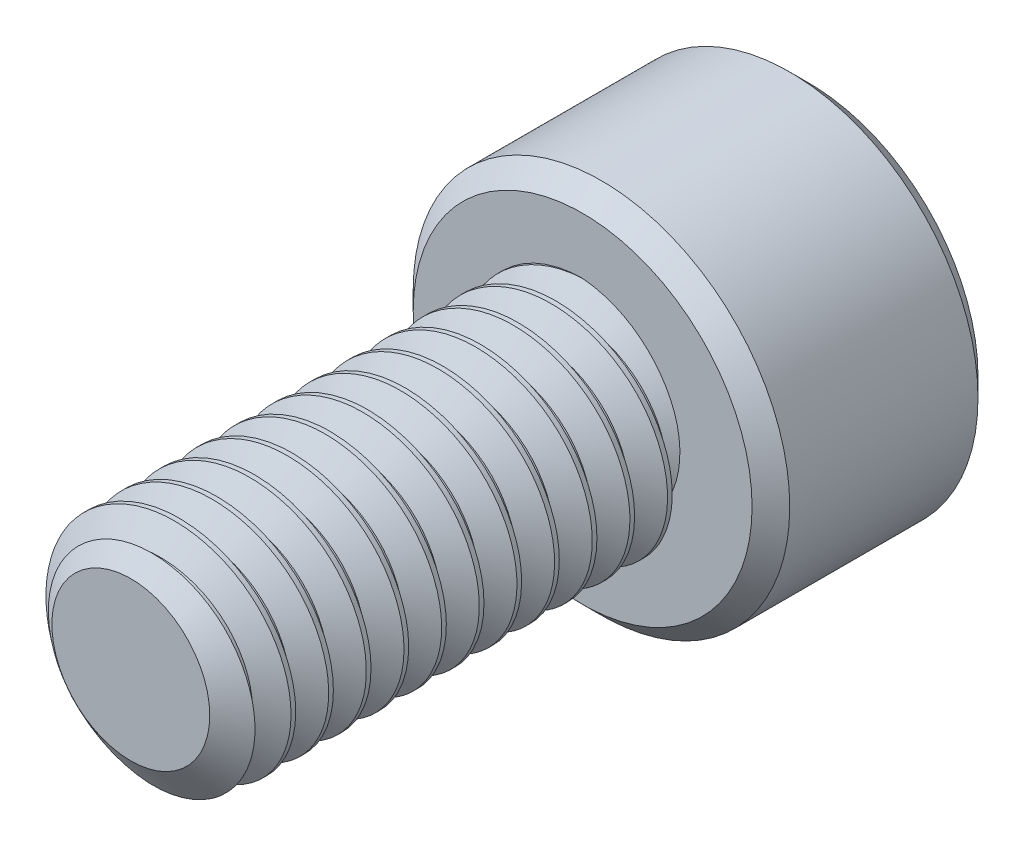
SolidWorks part; units mm, degrees
other "DetailItem1"
material "AISI Type 316L stainless steel"
ref_plane "Front Plane" through (0, 0, 0) normal (0, 0, 1) x (1, 0, 0)
ref_plane "Top Plane" through (0, 0, 0) normal (0, 1, 0) x (1, 0, 0)
ref_plane "Right Plane" through (0, 0, 0) normal (1, 0, 0) x (0, 0, -1)
sketch "Sketch1" plane through (0, 0, 0) normal (0, 0, 1) x (1, 0, 0)
  circle A0 centre (0, 0) radius 3
  dimension "OD" = 6
extrude "Extrude1" add sketch "Sketch1" against normal blind 12
sketch "Sketch2" plane through (0, 0, 0) normal (0, 0, 1) x (1, 0, 0)
  circle A0 centre (0, 0) radius 3 construction
  circle A1 centre (0, 0) radius 3
curve "Helix/Spiral1" pitch 1 height 13 turns 13 parameters "pitch"=1
sketch "Sketch3" plane through (0, 0, 0) normal (1, 0, 0) x (0, 0, -1)
  line L0 (-0.875, 3) -> (-0.5, 2.3505)
  line L1 (-0.5, 2.3505) -> (-0.375, 2.3505)
  line L2 (-0.375, 2.3505) -> (0, 3)
  line L3 (-0.875, 3) -> (0, 3)
  line L4 (-0.4375, 3) -> (-0.4375, 2.3505) construction
  line L5 (-0.6875, 2.6752) -> (-0.1875, 2.6752) construction
  line L6 (0, 3) -> (0, -3) construction
  dimension "D1" = 0.125
  dimension "D2" = 0.5
  dimension "D3" = 60
sweep "Cut-Sweep1" cut profiles "Sketch3" path "Helix/Spiral1"
sketch "Sketch4" plane through (0, 0, 0) normal (1, 0, 0) x (0, 0, -1)
  line L0 (0.6327, 3) -> (0, 2.0965)
  line L1 (0, 2.0965) -> (0, 3)
  line L2 (0.6327, 3) -> (0, 3)
  line L3 (-0.875, 3) -> (0, 3) construction
  line L4 (0, 0) -> (7.0209, 0) construction
  dimension "D1" = 55
  dimension "D2" = 0.254
revolve "Cut-Revolve1" cut sketch "Sketch4" angle 360 about L4
sketch "Sketch6" plane through (0, 0, -12) normal (0, 0, -1) x (-1, 0, 0)
  circle A0 centre (0, 0) radius 5
  dimension "head dia" = 10
extrude "Extrude2" add sketch "Sketch6" along normal blind 6
sketch "Sketch7" plane through (0, 0, -18) normal (0, 0, -1) x (-1, 0, 0)
  line L1 (0, 2.8868) -> (-2.5, 1.4434)
  line L2 (-2.5, 1.4434) -> (-2.5, -1.4434)
  line L3 (-2.5, -1.4434) -> (0, -2.8868)
  line L4 (0, -2.8868) -> (2.5, -1.4434)
  line L5 (2.5, -1.4434) -> (2.5, 1.4434)
  line L6 (2.5, 1.4434) -> (0, 2.8868)
  circle A0 centre (0, 0) radius 2.5 construction
  dimension "hex dia" = 5
extrude "Cut-Extrude1" cut sketch "Sketch7" against normal blind 3.75
sketch "Sketch8" plane through (0, 0, -18) normal (0, 0, -1) x (-1, 0, 0)
  circle A0 centre (0, 0) radius 2.8868
extrude "Cut-Extrude2" cut sketch "Sketch8" against normal through all draft 45
chamfer "Chamfer1" distance 0.5 angle 45 2 edges at (-5, 0, -18) (-5, 0, -12)
sketch "Sketch10" plane through (0, 0, -12) normal (0, 0, 1) x (1, 0, 0)
  circle A1 centre (0, 0) radius 3
  circle A2 centre (0, 0) radius 3
  dimension "D1" = 0
ref_plane "Plane1" through (0, 0, 0) normal (0, 0, 1) x (1, 0, 0)
extrude "partial thread" [suppressed] add sketch "Sketch10" along normal up to surface (31 mm away) separate body
chamfer "Chamfer2" [suppressed] distance 0.12 angle 45
combine bodies "Combine1" [suppressed] operation type add bodies to combine 107 108
sketch "Sketch9" plane through (0, 0, 0) normal (1, 0, 0) x (0, 0, -1)
  line L0 (0, 3) -> (0, -3) construction
  line L1 (2.5, 3) -> (2.5, -3) construction
  dimension "D1" = 2.5
equation "\"D3@Helix/Spiral1\" = \"screw length@Extrude1\"+\"pitch@Helix/Spiral1\""
equation "\"D1@Sketch3\" = \"pitch@Helix/Spiral1\"*.125"
equation "\"D2@Sketch3\" = \"pitch@Helix/Spiral1\"*.5"
equation "\"D1@Cut-Extrude1\" = \"hex dia@Sketch7\"*.75"
equation "\"D1@Chamfer1\" = \"head dia@Sketch6\"*.05"
equation "\"D1@Sketch9\" = \"pitch@Helix/Spiral1\"*2.5"
equation "\"D1@Chamfer2\"=\"OD@Sketch1\"*.02"
